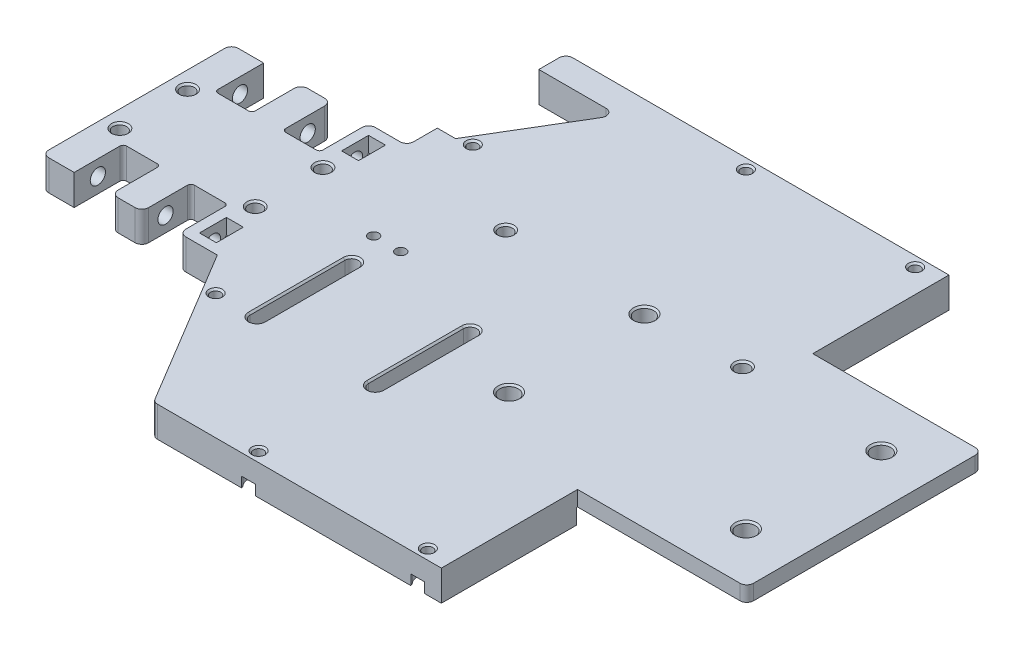
SolidWorks part; units mm, degrees
ref_plane "Front Plane" through (0, 0, 0) normal (0, 0, 1) x (1, 0, 0)
ref_plane "Top Plane" through (0, 0, 0) normal (0, 1, 0) x (1, 0, 0)
ref_plane "Right Plane" through (0, 0, 0) normal (1, 0, 0) x (0, 0, -1)
sketch "Sketch1" plane through (0, 0, 0) normal (0, 1, 0) x (1, 0, 0)
  line L0 (-78.0026, 25) -> (-28.0026, 25)
  line L1 (1.9974, 75) -> (86.9974, 75)
  line L2 (-78.0026, 25) -> (-78.0026, -25)
  line L3 (1.9974, -75) -> (86.9974, -75)
  line L4 (86.9974, 75) -> (86.9974, -75)
  line L7 (-28.0026, 25) -> (1.9974, 75)
  line L8 (1.9974, -75) -> (-28.0026, -25)
  line L9 (-28.0026, -25) -> (-78.0026, -25)
  point P0 (0, 0)
  dimension "D1" = 30
  dimension "D2" = 30
  dimension "D3" = 50
  dimension "D4" = 50
  dimension "D5" = 50
  dimension "D6" = 165
  dimension "D7" = 75
  dimension "D8" = 50
  dimension "D9" = 50
  dimension "D10" = 150
  dimension "D11" = 120.964
extrude "Boss-Extrude1" add sketch "Sketch1" along normal blind 9
sketch "Sketch3" plane through (0, 9, 0) normal (0, 1, 0) x (1, 0, 0)
  line L1 (-28.0026, 25) -> (-78.0026, 25) construction
  line L4 (-78.0026, 25) -> (-78.0026, -25) construction
  circle A0 centre (-73.0026, 10) radius 2
  circle A1 centre (-33.0026, 10) radius 2
  circle A2 centre (-33.0026, -10) radius 2
  circle A3 centre (-73.0026, -10) radius 2
  dimension "D5" = 4
  dimension "D6" = 4
  dimension "D7" = 4
  dimension "D8" = 4
  dimension "D1" = 40
  dimension "D2" = 20
  dimension "D3" = 20
  dimension "D4" = 40
  dimension "D9" = 15
  dimension "D10" = 5
  dimension "D11" = 15
  dimension "D12" = 5
extrude "Cut-Extrude1" cut sketch "Sketch3" against normal through all
sketch "Sketch4" plane through (86.9974, 0, 0) normal (1, 0, 0) x (0, 0, -1)
  line L0 (-75, 9) -> (75, 9) construction
  line L1 (-34.75, 9) -> (34.75, 9)
  line L2 (-34.75, 9) -> (-34.75, 4.5)
  line L3 (-34.75, 4.5) -> (34.75, 4.5)
  line L4 (34.75, 9) -> (34.75, 4.5)
  line L5 (-75, 9) -> (-75, 0) construction
  line L6 (75, 9) -> (75, 0) construction
  dimension "D1" = 4.5
  dimension "D2" = 40.25
  dimension "D3" = 40.25
  dimension "D4" = 69.5
extrude "Boss-Extrude2" add sketch "Sketch4" along normal blind 50
sketch "Sketch5" plane through (86.9974, 0, 0) normal (1, 0, 0) x (0, 0, -1)
  line L0 (-75, 0) -> (75, 0) construction
  line L1 (-35, 4.5) -> (35, 4.5)
  line L2 (-35, 4.5) -> (-35, 0)
  line L3 (-35, 0) -> (35, 0)
  line L4 (35, 4.5) -> (35, 0)
  line L6 (34.75, 4.5) -> (34.75, 9) construction
  dimension "D1" = 70
  dimension "D2" = 0.25
extrude "Cut-Extrude2" cut sketch "Sketch5" against normal blind 45
sketch "Sketch6" plane through (0, 9, 0) normal (0, 1, 0) x (1, 0, 0)
  line L2 (136.9974, 34.75) -> (136.9974, -34.75) construction
  circle A0 centre (51.9974, 20) radius 2.75
  circle A1 centre (51.9974, -20) radius 2.75
  circle A2 centre (121.9974, 20) radius 2.75
  circle A3 centre (121.9974, -20) radius 2.75
  dimension "D1" = 5.5
  dimension "D2" = 5.5
  dimension "D3" = 5.5
  dimension "D4" = 5.5
  dimension "D5" = 40
  dimension "D6" = 40
  dimension "D7" = 20
  dimension "D8" = 70
  dimension "D9" = 0
  dimension "D10" = 70
  dimension "D11" = 15
  dimension "D12" = 15
extrude "Cut-Extrude4" cut sketch "Sketch6" against normal blind 50
fillet "Fillet1" radius 2 4 edges at (-28.0026, 4.5, -25) (1.9974, 4.5, -75) (1.9974, 4.5, 75) (-28.0026, 4.5, 25)
chamfer "Chamfer1" distance 0.5 angle 45 4 edges at (51.9974, 9, 22.75) (121.9974, 9, 22.75) (121.9974, 9, -17.25) (51.9974, 9, -17.25)
fillet "Fillet2" radius 2 2 edges at (136.9974, 6.75, -34.75) (136.9974, 6.75, 34.75)
sketch "Sketch7" plane through (0, 9, 0) normal (0, 1, 0) x (1, 0, 0)
  line L0 (-78.0026, -25) -> (-29.1349, -25) construction
  line L1 (-68.5026, -25) -> (-57.5026, -25)
  line L2 (-68.5026, -25) -> (-68.5026, -13.5)
  line L3 (-68.5026, -13.5) -> (-57.5026, -13.5)
  line L4 (-57.5026, -25) -> (-57.5026, -13.5)
  line L5 (-78.0026, 25) -> (-78.0026, -25) construction
  line L6 (-48.5026, -25) -> (-37.5026, -25)
  line L7 (-48.5026, -25) -> (-48.5026, -13.5)
  line L8 (-48.5026, -13.5) -> (-37.5026, -13.5)
  line L9 (-37.5026, -25) -> (-37.5026, -13.5)
  dimension "D1" = 9.5
  dimension "D2" = 11
  dimension "D3" = 9
  dimension "D4" = 11
  dimension "D5" = 11.5
  dimension "D6" = 11.5
extrude "Cut-Extrude5" cut sketch "Sketch7" against normal through all
sketch "Sketch8" plane through (-78.0026, 0, 0) normal (-1, 0, 0) x (0, 0, 1)
  line L0 (-25, 9) -> (25, 9) construction
  line L1 (25, 9) -> (25, 0) construction
  circle A0 centre (21, 4.5) radius 2.25
  dimension "D2" = 4.5
  dimension "D1" = 4.5
  dimension "D3" = 4
extrude "Cut-Extrude6" cut sketch "Sketch8" against normal blind 50
sketch "Sketch10" plane through (-78.0026, 0, 0) normal (-1, 0, 0) x (0, 0, 1)
  circle A0 centre (21, 4.5) radius 3.5
  dimension "D1" = 7
extrude "Cut-Extrude8" cut sketch "Sketch10" against normal blind 4
sketch "Sketch11" plane through (-37.5026, 0, 0) normal (-1, 0, 0) x (0, 0, 1)
  line L42 (24.9837, 4.5) -> (24.9837, 16.2786)
  line L46 (17.0163, 4.5) -> (19.0081, 1.05)
  line L47 (19.0081, 1.05) -> (22.9919, 1.05)
  line L48 (22.9919, 1.05) -> (24.9837, 4.5)
  line L49 (24.9837, 16.2786) -> (17.0163, 16.2786)
  line L50 (17.0163, 16.2786) -> (17.0163, 4.5)
  line L52 (24.9837, 4.5) -> (23.9878, 6.225) [skipped]
  line L53 (22.9919, 7.95) -> (21, 7.95) [skipped]
  line L54 (19.0081, 7.95) -> (18.0122, 6.225) [skipped]
  arc A1 (18.0122, 2.775) -> (23.9878, 2.775) centre (21, 4.5) ccw construction
extrude "Cut-Extrude9" cut sketch "Sketch11" against normal blind 5 from offset 3 offset against normal yes
fillet "Fillet4" radius 1 4 edges at (-48.5026, 4.5, 13.5) (-37.5026, 4.5, 13.5) (-57.5026, 4.5, 13.5) (-68.5026, 4.5, 13.5)
mirror "Mirror2" about plane through (0, 0, 0) normal (0, 0, 1) of "Fillet4", "Cut-Extrude9", "Cut-Extrude8", "Cut-Extrude6", "Cut-Extrude5"
sketch "Sketch12" plane through (0, 9, 0) normal (0, 1, 0) x (1, 0, 0)
  line L0 (-6.5026, -10) -> (-6.5026, -38)
  line L1 (-2.5026, -10) -> (-2.5026, -38)
  line L2 (3.1298, -75) -> (86.9974, -75) construction
  line L3 (86.9974, -75) -> (86.9974, -34.75) construction
  line L4 (28.4974, -10) -> (28.4974, -38)
  line L5 (32.4974, -10) -> (32.4974, -38)
  arc A0 (-2.5026, -10) -> (-6.5026, -10) centre (-4.5026, -10) ccw
  arc A2 (-6.5026, -38) -> (-2.5026, -38) centre (-4.5026, -38) ccw
  arc A3 (32.4974, -10) -> (28.4974, -10) centre (30.4974, -10) ccw
  arc A4 (28.4974, -38) -> (32.4974, -38) centre (30.4974, -38) ccw
  dimension "D2" = 4
  dimension "D5" = 4
  dimension "D6" = 4
  dimension "D7" = 4
  dimension "D12" = 28
  dimension "D3" = 37
  dimension "D4" = 91.5
  dimension "D9" = 35
  dimension "D8" = 28
extrude "Cut-Extrude10" cut sketch "Sketch12" against normal blind 10
sketch "Sketch15" plane through (0, 9, 0) normal (0, 1, 0) x (1, 0, 0)
  line L0 (86.9974, 75) -> (3.1298, 75) construction
  line L2 (1.4148, 74.029) -> (-27.42, 25.971) construction
  line L3 (-4.95, 0) -> (4.95, 0) construction
  line L4 (86.9974, 34.75) -> (86.9974, 75) construction
  circle A0 centre (79.9974, 72) radius 1.5
  circle A1 centre (29.9974, 72) radius 1.5
  circle A2 centre (-16.704, 38) radius 1.5
  circle A7 centre (-16.704, -38) radius 1.5
  circle A8 centre (29.9974, -72) radius 1.5
  circle A9 centre (79.9974, -72) radius 1.5
  dimension "D1" = 3
  dimension "D2" = 3
  dimension "D3" = 3
  dimension "D4" = 37
  dimension "D5" = 50
  dimension "D6" = 3
  dimension "D7" = 3
  dimension "D8" = 3
  dimension "D9" = 7
extrude "Cut-Extrude12" cut sketch "Sketch15" against normal blind 10
sketch "Sketch17" plane through (0, 0, 0) normal (0, -1, 0) x (1, 0, 0)
  line L0 (4.95, 0) -> (-4.95, 0) construction
  circle A0 centre (29.9974, 72) radius 3.25
  circle A1 centre (-16.704, 38) radius 3.25
  circle A2 centre (79.9974, 72) radius 3.25
  circle A3 centre (79.9974, -72) radius 3.25
  circle A4 centre (-16.704, -38) radius 3.25
  circle A5 centre (29.9974, -72) radius 3.25
  dimension "D1" = 6.5
  dimension "D2" = 6.5
  dimension "D3" = 6.5
extrude "Cut-Extrude14" cut sketch "Sketch17" against normal blind 3
chamfer "Chamfer2" distance 1 angle 45 10 edges at (-19.9196, 1.5, 38.4716) (-18.6333, 1.5, 40.6154) (81.2474, 1.5, 75) (78.7474, 1.5, 75) (28.7474, 1.5, 75) (31.2474, 1.5, 75) (81.2474, 1.5, -75) (78.7474, 1.5, -75) (31.2474, 1.5, -75) (28.7474, 1.5, -75) first distance on face at (-16.5968, 1.5, 37.9357) first distance on face at (79.9974, 1.5, 71.875) first distance on face at (29.9974, 1.5, 71.875) first distance on face at (79.9974, 1.5, -71.875) first distance on face at (29.9974, 1.5, -71.875)
sketch "Sketch18" plane through (0, 0, 25) normal (0, 0, 1) x (1, 0, 0)
  line L1 (-37.5026, 9) -> (-25.5026, 9)
  line L2 (-37.5026, 9) -> (-37.5026, 0)
  line L3 (-37.5026, 0) -> (-25.5026, 0)
  line L4 (-25.5026, 9) -> (-25.5026, 0)
  dimension "D1" = 12
extrude "Boss-Extrude3" add sketch "Sketch18" along normal blind 3
mirror "Mirror3" about plane through (0, 0, 0) normal (0, 0, 1) of "Boss-Extrude3"
sketch "Sketch20" plane through (0, 9, 0) normal (0, 1, 0) x (1, 0, 0)
  line L0 (86.9974, 34.75) -> (86.9974, 75) construction
  line L2 (86.9974, 75) -> (3.1298, 75) construction
  circle A0 centre (9.9974, 21) radius 2
  circle A1 centre (79.9974, 21) radius 2
  dimension "D3" = 4
  dimension "D4" = 4
  dimension "D2" = 54
  dimension "D5" = 70
  dimension "D6" = 7
  dimension "D7" = 54
extrude "Cut-Extrude15" cut sketch "Sketch20" against normal through all
sketch "Sketch23" plane through (0, 0, 0) normal (1, 0, 0) x (0, 0, -1)
  line L0 (74.029, 0) -> (40.6154, 0) construction
  line L1 (75, 9) -> (67, 9)
  line L2 (75, 9) -> (75, 0)
  line L3 (75, 0) -> (67, 0)
  line L4 (67, 9) -> (67, 0)
  line L5 (74.029, 9) -> (28, 9) construction
  line L6 (28, 0) -> (37, 0)
  line L7 (28, 0) -> (28, 9)
  line L8 (28, 9) -> (37, 9)
  line L9 (37, 0) -> (37, 9)
  dimension "D1" = 8
  dimension "D2" = 9
extrude "Boss-Extrude5" add sketch "Sketch23" against normal up to vertex (26.2026 mm away) and the other way blind 3 up to point (-26.2026, 9, -28)
fillet "Fillet5" radius 2 1 edges at (-26.2026, 4.5, -28)
sketch "Sketch24" plane through (0, 0, 0) normal (0, -1, 0) x (1, 0, 0)
  circle A1 centre (29.9974, -72) radius 3.25
  circle A2 centre (-16.704, -38) radius 3.25
extrude "Cut-Extrude17" cut sketch "Sketch24" against normal up to surface (3 mm away) up to face at (29.9974, 3, -70.5)
sketch "Sketch25" plane through (0, 3, 0) normal (0, -1, 0) x (1, 0, 0)
  circle A1 centre (-16.704, -38) radius 1.5
extrude "Cut-Extrude18" cut sketch "Sketch25" against normal through all
sketch "Sketch26" plane through (-26.2026, 0, 0) normal (-1, 0, 0) x (0, 0, 1)
  line L0 (-75, 0) -> (-75, 9) construction
  line L1 (-75, 9) -> (-67, 9) construction
  circle A0 centre (-70, 4.5) radius 1.25
  circle A1 centre (-33, 4.5) radius 1.25
  dimension "D1" = 2.5
  dimension "D2" = 2.5
  dimension "D3" = 37
  dimension "D4" = 5
  dimension "D5" = 4.5
extrude "Cut-Extrude20" cut sketch "Sketch26" against normal blind 5
chamfer "Chamfer3" distance 1 angle 45 2 edges at (-18.6333, 1.5, -40.6154) (-19.9196, 1.5, -38.4716) first distance on face at (-16.5968, 1.5, -37.9357)
fillet "Fillet6" radius 2 2 edges at (-2.8026, 4.5, -67) (-26.2026, 4.5, -75)
chamfer "Chamfer4" distance 0.5 angle 45 20 edges at (79.9974, 9, 70.5) (79.9974, 9, -19) (79.9974, 9, -70.5) (29.9974, 9, -70.5) (-16.704, 9, -36.5) (-73.0026, 9, 12) (-73.0026, 9, -8) (-33.0026, 9, -8) (-33.0026, 9, 12) (-16.704, 9, 36.5) (29.9974, 9, 70.5) (-4.5026, 9, 40) (-4.5026, 9, 8) (9.9974, 9, -19) (30.4974, 9, 40) (30.4974, 9, 8) (32.4974, 9, 24) (28.4974, 9, 24) (-2.5026, 9, 24) (-6.5026, 9, 24)
sketch "Sketch27" plane through (0, 0, 0) normal (0, -1, 0) x (1, 0, 0)
  circle A0 centre (9.9974, -21) radius 3.5
  dimension "D1" = 7
extrude "Cut-Extrude21" cut sketch "Sketch27" against normal blind 3
sketch "Sketch28" plane through (0, 9, 0) normal (0, 1, 0) x (1, 0, 0)
  line L0 (-48.5026, 25) -> (-57.5026, 25) construction
  line L1 (-78.0026, 25) -> (-78.0026, -25) construction
  circle A0 centre (-8.0026, 0) radius 1.5
  circle A1 centre (-0.0026, 0) radius 1.5
  dimension "D3" = 3
  dimension "D4" = 3
  dimension "D1" = 25
  dimension "D2" = 25
  dimension "D5" = 70
  dimension "D6" = 8
extrude "Cut-Extrude22" cut sketch "Sketch28" against normal blind 10
sketch "Sketch29" plane through (0, 0, 0) normal (0, -1, 0) x (1, 0, 0)
  circle A0 centre (-8.0026, 0) radius 2.75
  circle A1 centre (-0.0026, 0) radius 2.75
  dimension "D1" = 5.5
  dimension "D2" = 5.5
extrude "Cut-Extrude23" cut sketch "Sketch29" against normal blind 3
sketch "Sketch30" plane through (0, 0, -25) normal (0, 0, -1) x (-1, 0, 0)
  line L1 (57.5026, 9) -> (48.5026, 9)
  line L2 (57.5026, 9) -> (57.5026, 0)
  line L3 (57.5026, 0) -> (48.5026, 0)
  line L4 (48.5026, 9) -> (48.5026, 0)
  line L5 (68.5026, 9) -> (78.0026, 9)
  line L6 (68.5026, 9) -> (68.5026, 0)
  line L7 (68.5026, 0) -> (78.0026, 0)
  line L8 (78.0026, 9) -> (78.0026, 0)
extrude "Boss-Extrude6" add sketch "Sketch30" along normal blind 3
mirror "Mirror4" about plane through (0, 0, 0) normal (0, 0, 1) of "Boss-Extrude6"
fillet "Fillet7" radius 2 8 edges at (-37.5026, 4.5, 28) (-37.5026, 4.5, -28) (-57.5026, 4.5, -28) (-48.5026, 4.5, -28) (-48.5026, 4.5, 28) (-57.5026, 4.5, 28) (-78.0026, 4.5, 28) (-78.0026, 4.5, -28)
fillet "Fillet8" radius 2 8 edges at (30.4974, 0, 8) (32.4974, 0, 24) (30.4974, 0, 40) (-4.5026, 0, 8) (-2.5026, 0, 24) (-4.5026, 0, 40) (28.4974, 0, 24) (-6.5026, 0, 24)
equation "\"D5@Sketch12\"=\"D2@Sketch12\""
